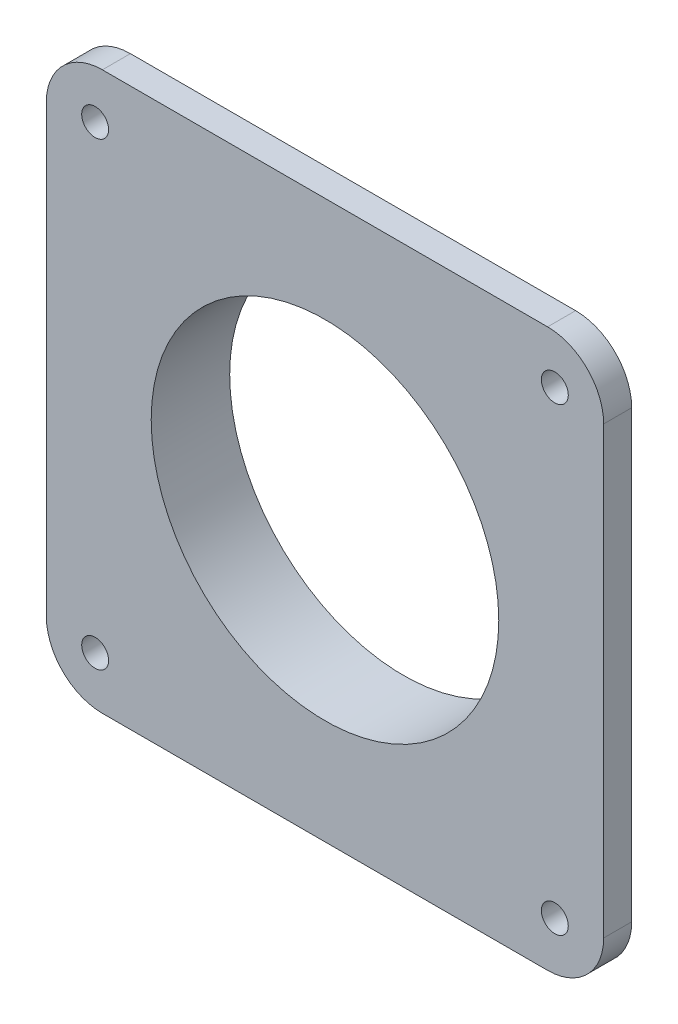
SolidWorks part; units mm, degrees
ref_plane "Front Plane" through (0, 0, 0) normal (0, 0, 1) x (1, 0, 0)
ref_plane "Top Plane" through (0, 0, 0) normal (0, 1, 0) x (1, 0, 0)
ref_plane "Right Plane" through (0, 0, 0) normal (1, 0, 0) x (0, 0, -1)
sketch "Model" plane through (0, 0, 0) normal (0, 0, 1) x (1, 0, 0)
  circle A0 centre (41, -41) radius 2.4
  circle A1 centre (-41, 41) radius 2.4
  circle A2 centre (41, 41) radius 2.4
  circle A3 centre (-41, -41) radius 2.4
  arc A4 (-31, 0) -> (31, 0) centre (0, 0) ccw
  arc A5 (31, 0) -> (-31, 0) centre (0, 0) ccw
  arc A6 (-32.5, -22.5167) -> (-45.5, -22.5167) centre (-39, -22.5167) ccw
  arc A7 (-45.5, -22.5167) -> (-32.5, -22.5167) centre (-39, -22.5167) ccw
  arc A8 (45.5, -22.5167) -> (32.5, -22.5167) centre (39, -22.5167) ccw
  arc A9 (32.5, -22.5167) -> (45.5, -22.5167) centre (39, -22.5167) ccw
  arc A10 (6.5, 45.0333) -> (-6.5, 45.0333) centre (0, 45.0333) ccw
  arc A11 (-6.5, 45.0333) -> (6.5, 45.0333) centre (0, 45.0333) ccw
  arc A12 (64.397, 0) -> (-64.397, 0) centre (0, 0) ccw
  arc A13 (-64.397, 0) -> (64.397, 0) centre (0, 0) ccw
sketch "Sketch2" plane through (0, 0, 0) normal (0, 0, 1) x (1, 0, 0)
  line L0 (41, -41) -> (0, 0) construction
  line L1 (-41, 41) -> (-49.7075, 49.7075) construction
  line L2 (-49.7075, 49.7075) -> (49.7075, 49.7075)
  line L3 (0, 0) -> (12.2984, 12.2984) construction
  line L4 (41, -41) -> (49.7075, -49.7075) construction
  line L5 (49.7075, -49.7075) -> (-49.7075, -49.7075)
  line L6 (-49.7075, -49.7075) -> (-49.7075, 49.7075)
  line L7 (49.7075, -49.7075) -> (49.7075, 49.7075)
  line L8 (-21.9203, 21.9203) -> (-41, 41) construction
  circle A0 centre (-41, 41) radius 2.4
  circle A1 centre (41, 41) radius 2.4
  circle A2 centre (41, -41) radius 2.4
  circle A3 centre (-41, -41) radius 2.4
  circle A4 centre (0, 0) radius 31
  point P21 (-109.3932, 33.5961)
extrude "Boss-Extrude1" add sketch "Sketch2" along normal blind 10
sketch "Sketch4" plane through (0, 0, 0) normal (0, 0, -1) x (-1, 0, 0)
  circle A0 centre (0, 0) radius 81.5685
extrude "Cut-Extrude1" cut sketch "Sketch4" against normal blind 5
fillet "Fillet1" radius 10 4 edges at (-49.7075, -49.7075, 7.5) (-49.7075, 49.7075, 7.5) (49.7075, 49.7075, 7.5) (49.7075, -49.7075, 7.5)
sketch "Sketch5" plane through (0, 0, 5) normal (0, 0, -1) x (-1, 0, 0)
  circle A0 centre (0, 0) radius 31
  circle A1 centre (0, 0) radius 35.1678
extrude "Boss-Extrude3" add sketch "Sketch5" along normal blind 9
fillet "Fillet2" radius 10 1 edges at (-35.1678, 0, 5)
